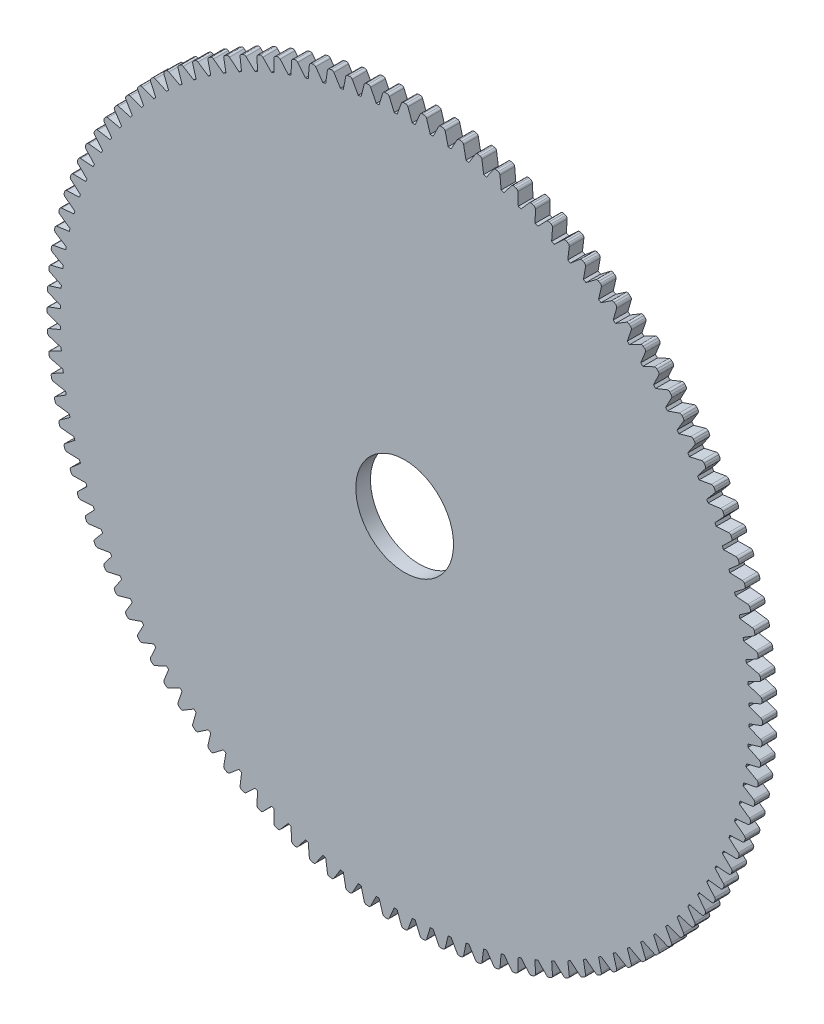
SolidWorks part; units mm, degrees
ref_plane "Front Plane" through (0, 0, 0) normal (0, 0, 1) x (1, 0, 0)
ref_plane "Top Plane" through (0, 0, 0) normal (0, 1, 0) x (1, 0, 0)
ref_plane "Right Plane" through (0, 0, 0) normal (1, 0, 0) x (0, 0, -1)
sketch "Sketch1" plane through (0, 0, 0) normal (0, 0, 1) x (1, 0, 0)
  circle A0 centre (0, 0) radius 70.5
  circle A1 centre (0, 0) radius 10
extrude "Boss-Extrude1" add sketch "Sketch1" along normal blind 3
sketch "Sketch2" plane through (0, 0, 3) normal (0, 0, 1) x (1, 0, 0)
  line L0 (0, 0) -> (0, 93.8108) construction
  line L1 (-0.6754, 72.8707) -> (-1.5796, 70.3864)
  line L2 (0.6754, 72.8707) -> (1.5796, 70.3864)
  arc A0 (-0.207, 73.1997) -> (0.207, 73.1997) centre (0, 0) cw
  arc A1 (-0.207, 73.1997) -> (-0.6754, 72.8707) centre (-0.2055, 72.6997) ccw
  arc A2 (0.207, 73.1997) -> (0.6754, 72.8707) centre (0.2055, 72.6997) cw
  arc A3 (1.5796, 70.3864) -> (-1.5796, 70.3864) centre (0, 59.4617) ccw
  point P10 (0, 73.2)
  dimension "D2" = 0.5
extrude "Boss-Extrude2" add sketch "Sketch2" against normal blind 3
pattern_circular "CirPattern1" count 120 over 360 about axis through (0, 0, 3) along (0, 0, 1) of "Boss-Extrude2"
